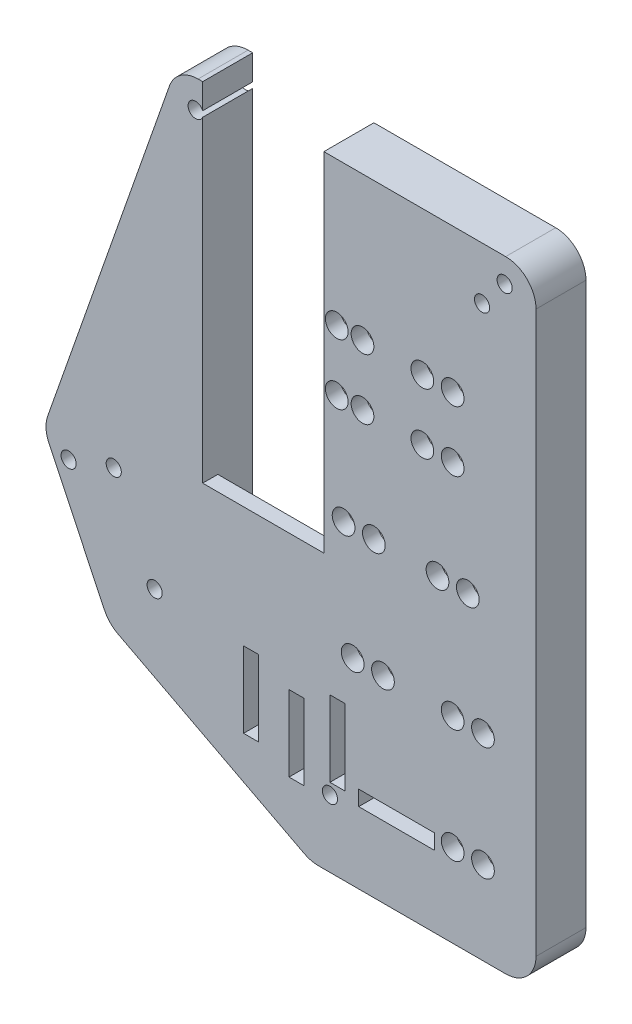
SolidWorks part; units mm, degrees
ref_plane "Front Plane" through (0, 0, 0) normal (0, 0, 1) x (1, 0, 0)
ref_plane "Top Plane" through (0, 0, 0) normal (0, 1, 0) x (1, 0, 0)
ref_plane "Right Plane" through (0, 0, 0) normal (1, 0, 0) x (0, 0, -1)
sketch "Sketch1" plane through (0, 0, 0) normal (0, 0, 1) x (1, 0, 0)
  line L6 (-20.066, -57.15) -> (46.99, -57.15) construction
  line L7 (-12.446, -73.152) -> (46.99, -73.152) construction
  line L8 (-3.3141, 6.35) -> (48.26, 6.35)
  line L9 (53.34, 1.27) -> (53.34, -92.71)
  line L10 (48.26, -97.79) -> (16.847, -97.79)
  line L16 (-8.1072, 2.9529) -> (-28.5162, -55.1739)
  line L18 (-20.066, -57.15) -> (-29.21, -57.15) construction
  line L26 (0, 0) -> (46.99, 0) construction
  line L27 (46.99, 0) -> (46.99, -88.9) construction
  line L28 (46.99, -88.9) -> (17.78, -88.9) construction
  line L29 (17.78, -88.9) -> (-12.446, -73.152) construction
  line L30 (-12.446, -73.152) -> (-20.066, -57.15) construction
  line L31 (-20.066, -57.15) -> (0, 0) construction
  line L32 (46.99, -57.15) -> (46.99, -88.9) construction
  line L33 (17.78, -88.9) -> (15.603, -97.79) construction
  line L34 (-12.446, -73.152) -> (-17.9301, -78.4424) construction
  line L35 (14.4997, -97.2152) -> (-16.7505, -80.9336)
  line L36 (-28.3096, -59.0409) -> (-18.9898, -78.6124)
  arc A0 (53.34, -92.71) -> (48.26, -97.79) centre (48.26, -92.71) cw
  arc A1 (14.4997, -97.2152) -> (16.847, -97.79) centre (16.847, -92.71) ccw
  arc A2 (-16.7505, -80.9336) -> (-18.9898, -78.6124) centre (-14.4033, -76.4284) cw
  arc A3 (-28.5162, -55.1739) -> (-28.3096, -59.0409) centre (-23.723, -56.8568) ccw
  arc A4 (-8.1072, 2.9529) -> (-3.3141, 6.35) centre (-3.3141, 1.27) cw
  arc A5 (48.26, 6.35) -> (53.34, 1.27) centre (48.26, 1.27) cw
  point P13 (53.34, -97.79)
  point P30 (53.34, 6.35)
  dimension "D8" = 5.08
  dimension "D1" = 88.9
  dimension "D2" = 29.21
  dimension "D3" = 59.436
  dimension "D4" = 67.056
  dimension "D5" = 104.14
  dimension "D6" = 82.55
  dimension "D7" = 46.99
  dimension "D13" = 103.76
  dimension "D17" = 108.51
extrude "Boss-Extrude1" add sketch "Sketch1" along normal blind 2.54
sketch "Sketch3" plane through (0, 0, 0) normal (0, 0, 1) x (1, 0, 0)
  line L8 (0, 0) -> (46.99, 0) construction
  line L9 (46.99, 0) -> (46.99, -88.9) construction
  line L10 (46.99, -88.9) -> (17.78, -88.9) construction
  line L11 (17.78, -88.9) -> (-12.446, -73.152) construction
  line L12 (-12.446, -73.152) -> (-20.066, -57.15) construction
  line L13 (-20.066, -57.15) -> (0, 0) construction
sketch "Sketch4" plane through (0, 0, 0) normal (0, 0, -1) x (-1, 0, 0)
  line L8 (-17.78, -1.143) -> (2.54, -1.143)
  line L9 (-17.78, -1.143) -> (-17.78, -51.943)
  line L10 (-17.78, -51.943) -> (2.54, -51.943)
  line L11 (2.54, -1.143) -> (2.54, -51.943)
  circle A0 centre (-39.37, -17.78) radius 1.905
  circle A1 centre (-34.29, -17.78) radius 1.905
  circle A2 centre (-39.37, -27.94) radius 1.905
  circle A3 centre (-34.29, -27.94) radius 1.905
  circle A4 centre (-41.91, -45.72) radius 1.905
  circle A5 centre (-36.83, -45.72) radius 1.905
  circle A6 centre (-44.45, -64.77) radius 1.905
  circle A7 centre (-39.37, -64.77) radius 1.905
  circle A8 centre (-44.45, -83.82) radius 1.905
  circle A9 centre (-39.37, -83.82) radius 1.905
  circle A10 centre (-24.257, -17.78) radius 1.905
  circle A11 centre (-19.939, -17.78) radius 1.905
  circle A12 centre (-24.257, -27.94) radius 1.905
  circle A13 centre (-19.939, -27.94) radius 1.905
  circle A14 centre (-26.162, -45.72) radius 1.905
  circle A15 centre (-21.082, -45.72) radius 1.905
  circle A16 centre (-27.686, -64.77) radius 1.905
  circle A17 centre (-22.606, -64.77) radius 1.905
  dimension "D1" = 3.81
  dimension "D2" = 3.81
  dimension "D6" = 3.81
  dimension "D7" = 3.81
  dimension "D11" = 3.81
  dimension "D12" = 3.81
  dimension "D16" = 3.81
  dimension "D17" = 3.81
  dimension "D21" = 3.81
  dimension "D22" = 3.81
  dimension "D30" = 3.81
  dimension "D31" = 3.81
  dimension "D35" = 3.81
  dimension "D36" = 3.81
  dimension "D40" = 3.81
  dimension "D41" = 3.81
  dimension "D45" = 3.81
  dimension "D46" = 3.81
  dimension "D3" = 5.08
  dimension "D8" = 5.08
  dimension "D13" = 5.08
  dimension "D18" = 5.08
  dimension "D23" = 5.08
  dimension "D26" = 50.8
  dimension "D27" = 20.32
  dimension "D32" = 4.318
  dimension "D37" = 4.318
  dimension "D42" = 5.08
  dimension "D47" = 5.08
extrude "Cut-Extrude2" cut sketch "Sketch4" against normal blind 25.4
sketch "Sketch5" plane through (0, 0, 2.54) normal (0, 0, 1) x (1, 0, 0)
  line L0 (-2.54, -1.143) -> (-2.54, 6.35)
  line L1 (48.26, 6.35) -> (-3.3141, 6.35) construction
  line L2 (17.78, -1.143) -> (17.78, 6.35)
  line L3 (17.78, 6.35) -> (-2.54, 6.35)
  line L4 (-2.54, -1.143) -> (17.78, -1.143)
extrude "Cut-Extrude3" cut sketch "Sketch5" against normal blind 5.08
sketch "Sketch6" plane through (0, 0, 2.54) normal (0, 0, 1) x (1, 0, 0)
  line L0 (0, 0) -> (46.99, 0) construction
  line L1 (46.99, 0) -> (46.99, -88.9) construction
  line L2 (17.78, -88.9) -> (17.78, -82.3142) construction
  line L3 (46.99, -88.9) -> (17.78, -88.9) construction
  circle A0 centre (1.6002, -2.4384) radius 1.27
  circle A1 centre (44.2976, -2.4384) radius 1.27
  circle A2 centre (-17.4498, -57.15) radius 1.27
  circle A4 centre (-10.5918, -71.3486) radius 1.27
  circle A5 centre (18.796, -86.5378) radius 1.27
  dimension "D1" = 2.54
  dimension "D3" = 2.54
  dimension "D7" = 2.54
  dimension "D9" = 2.54
  dimension "D11" = 2.54
  dimension "D2" = 2.4384
  dimension "D4" = 2.4384
  dimension "D5" = 2.6924
  dimension "D6" = 45.3898
  dimension "D8" = 2.6162
  dimension "D10" = 2.5866
  dimension "D12" = 1.016
  dimension "D13" = 2.3622
sketch "Sketch8" plane through (0, 0, 2.54) normal (0, 0, 1) x (1, 0, 0)
  line L0 (46.99, 0) -> (46.99, -88.9) construction
  line L1 (23.622, -83.2866) -> (36.322, -83.2866)
  line L2 (23.622, -83.2866) -> (23.622, -85.8266)
  line L3 (23.622, -85.8266) -> (36.322, -85.8266)
  line L4 (36.322, -83.2866) -> (36.322, -85.8266)
  line L5 (0, 0) -> (46.99, 0) construction
  line L7 (18.796, -72.009) -> (21.336, -72.009)
  line L8 (18.796, -72.009) -> (18.796, -84.709)
  line L9 (18.796, -84.709) -> (21.336, -84.709)
  line L10 (21.336, -72.009) -> (21.336, -84.709)
  line L11 (11.938, -74.676) -> (14.478, -74.676)
  line L12 (11.938, -74.676) -> (11.938, -87.376)
  line L13 (11.938, -87.376) -> (14.478, -87.376)
  line L14 (14.478, -74.676) -> (14.478, -87.376)
  line L15 (4.318, -72.136) -> (6.858, -72.136)
  line L16 (4.318, -72.136) -> (4.318, -84.836)
  line L17 (4.318, -84.836) -> (6.858, -84.836)
  line L18 (6.858, -72.136) -> (6.858, -84.836)
  dimension "D1" = 12.7
  dimension "D2" = 2.54
  dimension "D3" = 10.668
  dimension "D4" = 83.2866
  dimension "D5" = 12.7
  dimension "D6" = 2.54
  dimension "D7" = 25.654
  dimension "D8" = 72.009
  dimension "D9" = 12.7
  dimension "D10" = 2.54
  dimension "D11" = 32.512
  dimension "D12" = 74.676
  dimension "D13" = 12.7
  dimension "D14" = 2.54
  dimension "D15" = 72.136
  dimension "D16" = 40.132
extrude "Cut-Extrude5" cut sketch "Sketch8" against normal blind 5.08
sketch "Sketch9" plane through (0, 0, 0) normal (0, 0, -1) x (-1, 0, 0)
  line L0 (-48.26, -97.79) -> (-48.26, 1.27)
  line L1 (-48.26, 1.27) -> (-17.78, 1.27)
  line L2 (-17.78, 1.27) -> (-17.78, 6.35)
  line L3 (-17.78, 6.35) -> (-48.26, 6.35)
  line L4 (-53.34, -92.71) -> (-53.34, 1.27) construction
  line L5 (-53.34, 1.27) -> (-53.34, -92.71)
  line L6 (-17.78, 6.35) -> (-17.78, -51.943) construction
  line L7 (-48.26, 6.35) -> (-17.78, 6.35) construction
  line L9 (2.54, 0.8204) -> (2.54, -82.6092)
  line L12 (2.54, -51.943) -> (2.54, 6.35) construction
  line L13 (2.54, 0.8204) -> (2.54, 6.35)
  line L14 (3.3141, 6.35) -> (2.54, 6.35)
  line L15 (8.1072, 2.9529) -> (28.5162, -55.1739)
  line L17 (28.3096, -59.0409) -> (18.9898, -78.6124)
  line L18 (16.7505, -80.9336) -> (-14.4997, -97.2152)
  line L19 (-16.847, -97.79) -> (-16.847, -92.71)
  line L20 (-16.847, -92.71) -> (2.54, -82.6092)
  arc A0 (-53.34, -92.71) -> (-48.26, -97.79) centre (-48.26, -92.71) ccw
  arc A1 (-16.847, -97.79) -> (-14.4997, -97.2152) centre (-16.847, -92.71) ccw
  arc A2 (16.7505, -80.9336) -> (18.9898, -78.6124) centre (14.4033, -76.4284) ccw
  arc A3 (28.3096, -59.0409) -> (28.5162, -55.1739) centre (23.723, -56.8568) ccw
  arc A4 (3.3141, 6.35) -> (8.1072, 2.9529) centre (3.3141, 1.27) cw
  arc A5 (-48.26, 6.35) -> (-53.34, 1.27) centre (-48.26, 1.27) ccw
  dimension "D3" = 5.08
  dimension "D1" = 5.08
  dimension "D2" = 5.08
extrude "Boss-Extrude2" add sketch "Sketch9" along normal blind 5.842
sketch "Sketch10" plane through (0, 0, 2.54) normal (0, 0, 1) x (1, 0, 0)
  line L0 (48.26, 6.35) -> (17.78, 6.35) construction
  line L1 (53.34, -92.71) -> (53.34, 1.27) construction
  line L2 (-2.54, 6.35) -> (-3.3141, 6.35) construction
  line L3 (-8.1072, 2.9529) -> (-28.5162, -55.1739) construction
  line L4 (-28.3096, -59.0409) -> (-18.9898, -78.6124) construction
  circle A0 centre (48.0822, 2.286) radius 1.27
  circle A1 centre (-3.7187, 1.651) radius 1.27
  circle A2 centre (-25.0123, -59.762) radius 1.27
  dimension "D1" = 2.54
  dimension "D2" = 4.064
  dimension "D3" = 5.2578
  dimension "D4" = 4.699
  dimension "D5" = 4.572
  dimension "D6" = 2.667
  dimension "D7" = 4.826
extrude "Cut-Extrude6" cut sketch "Sketch10" against normal through all both and the other way through all
extrude "Cut-Extrude7" cut sketch "Sketch6" against normal through all both and the other way through all
